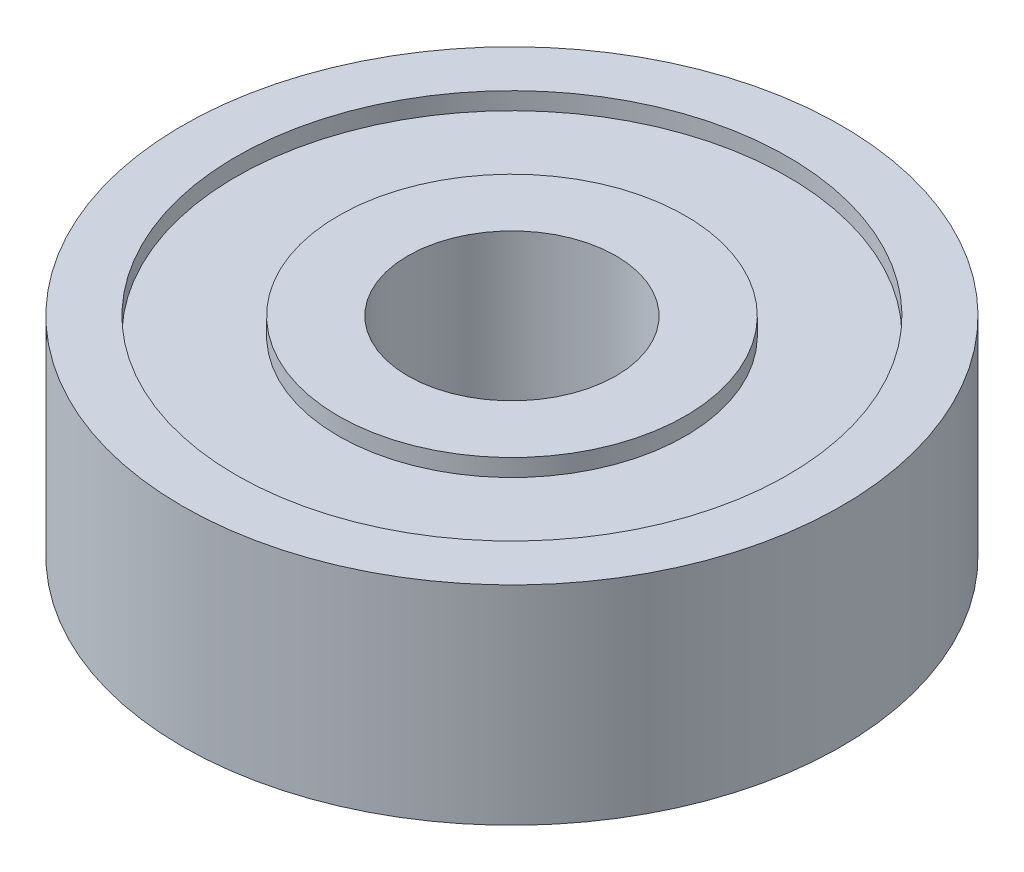
SolidWorks part; units mm, degrees
ref_plane "Front Plane" through (0, 0, 0) normal (0, 0, 1) x (1, 0, 0)
ref_plane "Top Plane" through (0, 0, 0) normal (0, 1, 0) x (1, 0, 0)
ref_plane "Right Plane" through (0, 0, 0) normal (1, 0, 0) x (0, 0, -1)
sketch "Sketch1" plane through (0, 0, 0) normal (0, 1, 0) x (1, 0, 0)
  circle A0 centre (0, 0) radius 3
  circle A1 centre (0, 0) radius 9.5
extrude "Boss-Extrude1" add sketch "Sketch1" along normal blind 6
sketch "Sketch2" plane through (0, 6, 0) normal (0, 1, 0) x (1, 0, 0)
  circle A0 centre (0, 0) radius 5.0015
  circle A1 centre (0, 0) radius 7.95
extrude "Cut-Extrude1" cut sketch "Sketch2" against normal blind 0.5
sketch "Sketch3" plane through (0, 0, 0) normal (0, -1, 0) x (1, 0, 0)
  circle A0 centre (0, 0) radius 5.0025
  circle A1 centre (0, 0) radius 7.95
extrude "Cut-Extrude2" cut sketch "Sketch3" against normal blind 0.5
move or copy body "Body-Move/Copy1" [suppressed] bodies to move or copy 103
